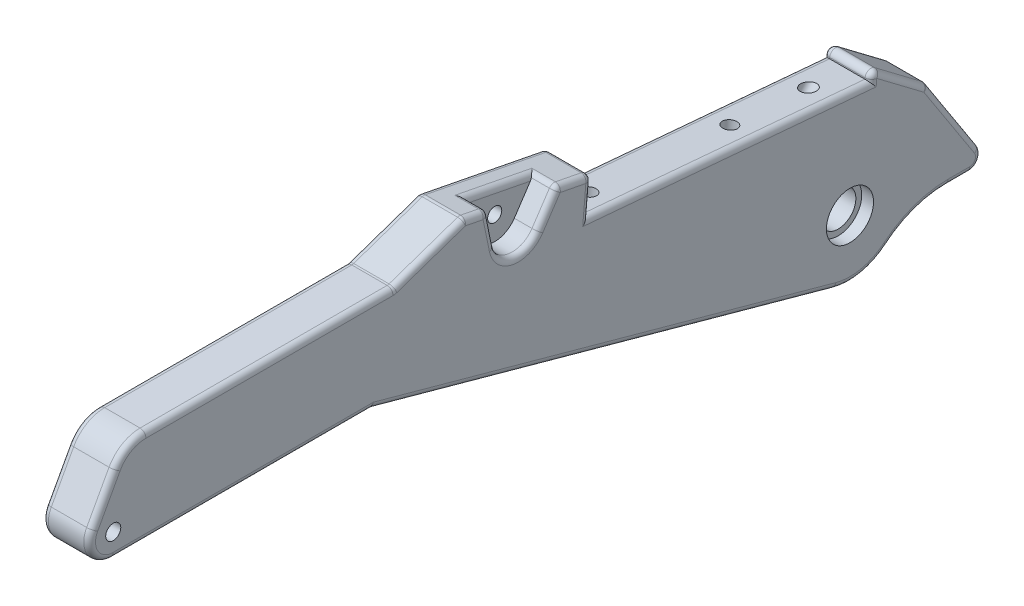
SolidWorks part; units mm, degrees
ref_plane "Front Plane" through (0, 0, 0) normal (0, 0, 1) x (1, 0, 0)
ref_plane "Top Plane" through (0, 0, 0) normal (0, 1, 0) x (1, 0, 0)
ref_plane "Right Plane" through (0, 0, 0) normal (1, 0, 0) x (0, 0, -1)
sketch "Sketch1" plane through (0, 0, 0) normal (1, 0, 0) x (0, 0, -1)
  line L0 (-5.5746, 3.0408) -> (3.158, 19.05)
  line L1 (3.158, 19.05) -> (75.6627, 19.05)
  line L3 (129.0542, 18.9233) -> (128.2241, 9.4345)
  line L4 (128.2241, 9.4345) -> (204.1341, 2.7933)
  line L6 (0, -6.35) -> (69.85, -6.35)
  line L8 (-5.5746, 3.0408) -> (7.9306, 27.7995) construction
  line L9 (129.0542, 18.9233) -> (94.7762, 25.6144)
  line L10 (94.7762, 25.6144) -> (75.6627, 19.05)
  line L12 (70.0006, 30.4506) -> (127.6524, 19.1969) construction
  line L15 (128.3624, 11.016) -> (128.9159, 17.3418) construction
  line L24 (219.6164, -5.5196) -> (233.4447, -26.8477) construction
  line L26 (219.7687, -5.7545) -> (233.4447, -26.8477)
  line L29 (69.85, 30.48) -> (129.0542, 18.9233) construction
  line L30 (206.6988, 4.2294) -> (219.393, -5.351) construction
  line L31 (204.1341, 2.7933) -> (204.161, 3.1007) construction
  line L32 (230.7807, -31.75) -> (224.8967, -31.75) construction
  line L33 (194.299, -40.7027) -> (69.85, -6.35) construction
  line L34 (206.6988, 4.2294) -> (219.393, -5.351)
  line L35 (204.1341, 2.7933) -> (204.161, 3.1007)
  line L36 (230.7807, -31.75) -> (224.8967, -31.75)
  line L37 (194.299, -40.7027) -> (69.85, -6.35)
  line L39 (-5.5746, 3.0408) -> (7.9306, 27.7995) construction
  circle A0 centre (0, 0) radius 2.032
  arc A1 (-5.5746, 3.0408) -> (0, -6.35) centre (0, 0) ccw
  arc A3 (0, -6.35) -> (-5.5746, 3.0408) centre (0, 0) ccw construction
  arc A12 (230.7807, -31.75) -> (233.4447, -26.8477) centre (230.7807, -28.575) ccw construction
  arc A13 (230.7807, -31.75) -> (233.4447, -26.8477) centre (230.7807, -28.575) ccw
  arc A14 (206.6988, 4.2294) -> (204.161, 3.1007) centre (205.7425, 2.9623) ccw construction
  arc A15 (224.8967, -31.75) -> (208.6668, -37.6115) centre (224.8967, -57.15) ccw construction
  arc A16 (194.299, -40.7027) -> (208.6668, -37.6115) centre (198.5232, -25.4) ccw construction
  arc A17 (206.6988, 4.2294) -> (204.161, 3.1007) centre (205.7425, 2.9623) ccw
  arc A18 (224.8967, -31.75) -> (208.6668, -37.6115) centre (224.8967, -57.15) ccw
  arc A19 (194.299, -40.7027) -> (208.6668, -37.6115) centre (198.5232, -25.4) ccw
  arc A20 (219.7687, -5.7545) -> (219.393, -5.351) centre (218.4366, -6.6181) ccw construction
  arc A21 (219.7687, -5.7545) -> (219.393, -5.351) centre (218.4366, -6.6181) ccw
  dimension "D1" = 4.064
  dimension "D2" = 19.05
  dimension "D3" = 30
  dimension "D4" = 34.925
extrude "Boss-Extrude1" add sketch "Sketch1" along normal blind 12.7
fillet "Fillet1" radius 9.525 1 edges at (6.35, 19.05, -3.158)
sketch "Sketch2" plane through (0, 0, 0) normal (-1, 0, 0) x (0, 0, 1)
  circle A0 centre (-198.5232, -25.4) radius 4.7625
  circle A3 centre (-198.5232, -25.4) radius 6.35 construction
  dimension "D1" = 9.525
extrude "Cut-Extrude1" cut sketch "Sketch2" against normal through all
sketch "Sketch4" plane through (12.7, 0, 0) normal (1, 0, 0) x (0, 0, -1)
  circle A0 centre (198.5232, -25.4) radius 6.35
  dimension "D1" = 12.7
extrude "Cut-Extrude2" cut sketch "Sketch4" against normal blind 3.175
sketch "Sketch9" plane through (12.7, 0, 0) normal (1, 0, 0) x (0, 0, -1)
  line L0 (102.9197, 15.0665) -> (101.0086, 24.3978)
  line L2 (114.4256, 12.8206) -> (119.7057, 20.7481)
  line L3 (101.0086, 24.3978) -> (119.7057, 20.7481)
  line L4 (129.0542, 18.9233) -> (94.7762, 25.6144) construction
  arc A0 (102.9197, 15.0665) -> (114.4256, 12.8206) centre (109.1406, 16.3406) ccw
  dimension "D1" = 12.7
  dimension "D2" = 9.525
  dimension "D3" = 19.05
extrude "Cut-Extrude6" cut sketch "Sketch9" against normal blind 6.35
sketch "Sketch10" plane through (6.35, 0, 0) normal (1, 0, 0) x (0, 0, -1)
  circle A0 centre (109.1406, 16.3406) radius 1.905
  arc A1 (102.9197, 15.0665) -> (114.4256, 12.8206) centre (109.1406, 16.3406) ccw construction
  dimension "D1" = 3.81
extrude "Cut-Extrude7" cut sketch "Sketch10" against normal through all
fillet "Fillet2" radius 1.5875 48 edges at (0, 2.947, -204.1476) (0, 4.4128, -205.0973) (0, -0.5608, -213.0459) (0, -5.5363, -219.5985) (0, -16.3011, -226.6067) (0, -30.091, -233.5704) (0, -31.75, -227.8387) (0, -33.2603, -216.2687) (0, -40.9199, -201.8622) (0, -6.35, -34.925) (0, -3.2414, 5.4604) (0, 8.5635, 2.5621) (0, 17.7156, -3.9501) (12.7, 2.947, -204.1476) (12.7, 4.4128, -205.0973) (12.7, -0.5608, -213.0459) (12.7, -5.5363, -219.5985) (12.7, -16.3011, -226.6067) (12.7, -30.091, -233.5704) (12.7, -31.75, -227.8387) (12.7, -33.2603, -216.2687) (12.7, -40.9199, -201.8622) (12.7, -6.35, -34.925) (12.7, -3.2414, 5.4604) (12.7, 8.5635, 2.5621) (12.7, 17.7156, -3.9501) (0, -23.5263, -132.0745) (0, 6.1139, -166.1791) (0, 14.1789, -128.6392) (0, 19.05, -42.2375) (12.7, -23.5263, -132.0745) (12.7, 6.1139, -166.1791) (12.7, 14.1789, -128.6392) (12.7, 19.05, -42.2375) (12.7, 19.7322, -101.9641) (12.7, 16.7843, -117.0656) (12.7, 10.1082, -107.924) (12.7, 19.8357, -124.38) (0, 22.2688, -111.9152) (9.525, 20.7481, -119.7057) (9.525, 24.3978, -101.0086) (6.35, 22.573, -110.3571) (12.7, 25.0061, -97.8924) (12.7, 22.3322, -85.2195) (0, 22.3322, -85.2195) (6.35, 25.6144, -94.7762) (6.35, 19.05, -75.6627) (6.35, 18.9233, -129.0542)
sketch "Sketch6" plane through (0, 102.0823, -77.0424) normal (0, 0.7982, -0.6024) x (1, 0, 0)
  circle A0 centre (6.35, 152.3647) radius 1.905
  circle A1 centre (6.35, 152.3647) radius 2.286 construction
  dimension "D1" = 3.81
extrude "Cut-Extrude3" cut sketch "Sketch6" against normal blind 25.4
sketch "Sketch7" plane through (0, 20.4958, -1.7931) normal (0, 0.9962, -0.0872) x (1, 0, 0)
  circle A0 centre (6.35, 171.3639) radius 1.905
  circle A1 centre (6.35, 133.2639) radius 1.905
  circle A2 centre (6.35, 133.2639) radius 2.286 construction
  circle A3 centre (6.35, 171.3639) radius 2.286 construction
  dimension "D1" = 3.81
extrude "Cut-Extrude4" cut sketch "Sketch7" against normal blind 15.875
sketch "Sketch8" plane through (0, 98.6153, -152.0993) normal (0, 0.544, -0.8391) x (-1, 0, 0)
  circle A0 centre (-6.35, -139.9823) radius 1.905
  circle A1 centre (-6.35, -139.9823) radius 2.286 construction
  dimension "D1" = 3.81
extrude "Cut-Extrude5" cut sketch "Sketch8" against normal blind 12.7
